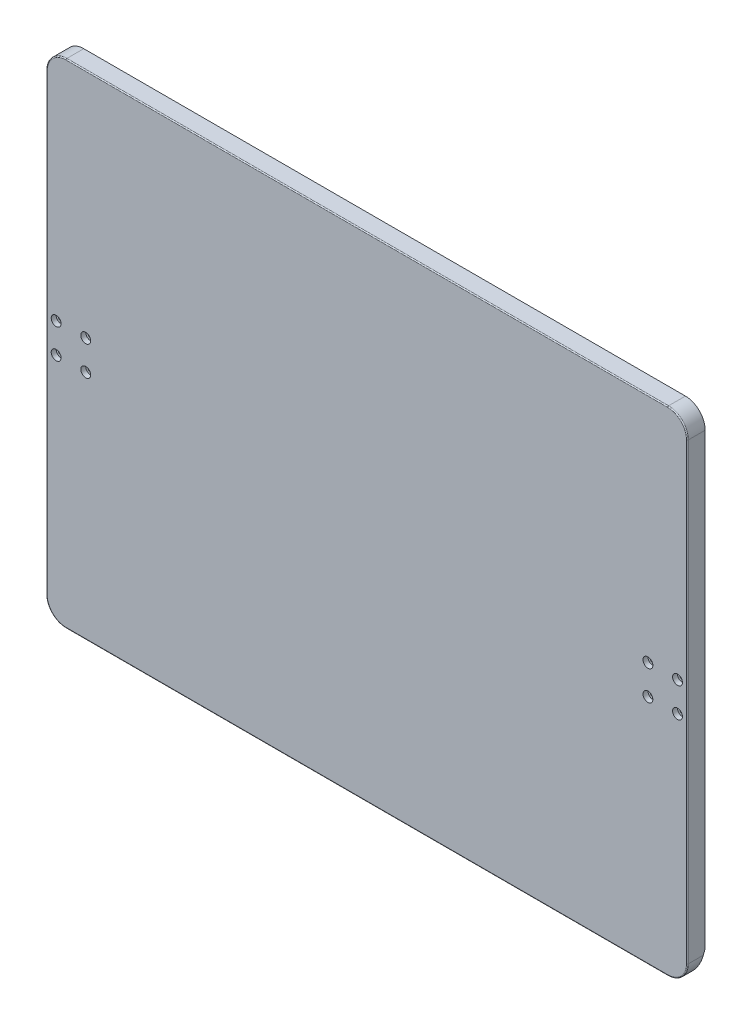
SolidWorks part; units mm, degrees
material "Beech"
ref_plane "Front Plane" through (0, 0, 0) normal (0, 0, 1) x (1, 0, 0)
ref_plane "Top Plane" through (0, 0, 0) normal (0, 1, 0) x (1, 0, 0)
ref_plane "Right Plane" through (0, 0, 0) normal (1, 0, 0) x (0, 0, -1)
sketch "Sketch1" plane through (0, 0, 0) normal (0, 0, 1) x (1, 0, 0)
  line L1 (0, 0) -> (650, 0)
  line L2 (0, 0) -> (0, 500)
  line L3 (0, 500) -> (650, 500)
  line L4 (650, 0) -> (650, 500)
  dimension "D1" = 500
  dimension "D2" = 650
extrude "base" add sketch "Sketch1" along normal blind 18
hole_wizard "counterbored M5 bolt holes" positions "Sketch2" profile "Sketch3" counterbore size "M5" standard "ANSI Metric" end condition through all
sketch "Sketch2" plane through (0, 0, 18) normal (0, 0, 1) x (1, 0, 0)
  line L1 (10, 265) -> (40, 265)
  line L2 (10, 265) -> (10, 235)
  line L3 (10, 235) -> (40, 235)
  line L4 (40, 265) -> (40, 235)
  line L5 (10, 250) -> (0, 250)
  line L6 (0, 500) -> (0, 0) construction
  point P1 (10, 265)
  point P2 (40, 235)
  point P41 (10, 235)
  point P42 (40, 265)
  dimension "D1" = 30
  dimension "D2" = 30
  dimension "D3" = 10
sketch "Sketch3" plane through (10, 265, 18) normal (1, 0, 0) x (0, -1, 0)
  line L0 (0, 0) -> (0, 18)
  line L1 (0, 18) -> (2.75, 18)
  line L3 (2.75, 18) -> (2.75, 5)
  line L4 (2.75, 5) -> (5, 5)
  line L5 (5, 5) -> (5, 0)
  line L7 (5, 0) -> (0, 0)
  line L11 (0, -6.35) -> (0, 107.95) construction
  dimension "Thru Hole Dia." = 5.5
  dimension "Thru Hole Depth" = 18
  dimension "C'Bore Dia." = 10
  dimension "C'Bore Depth" = 5
ref_plane "midplane in x" through (325, 0, 0) normal (-1, 0, 0) x (0, 0, 1)
mirror "mirror counterbored bolt holes" about plane through (325, 0, 0) normal (-1, 0, 0) of "counterbored M5 bolt holes"
fillet "round corners" radius 20 4 edges at (0, 500, 9) (650, 500, 9) (650, 0, 9) (0, 0, 9)
fillet "break top edge" radius 1 8 edges at (5.8579, 494.1421, 18) (325, 500, 18) (644.1421, 494.1421, 18) (650, 250, 18) (644.1421, 5.8579, 18) (325, 0, 18) (5.8579, 5.8579, 18) (0, 250, 18)
chamfer "front shadow chamfer" distance 25 angle 20 1 edges at (325, 0, 0) tangent propagation no first distance on face at (642.75, 265, 0)
fillet "round chamfer edges" [suppressed] radius 1
equation "\"board_thickness\" = 18mm"
equation "\"way_width\"= 75mm"
equation "\"way_thickness\"= 50mm"
equation "\"radial_clearance\"= 0.1mm"
equation "\"slider_width\"= \"way_width\"-2* \"radial_clearance\""
equation "\"slider_thickness\" = \"way_thickness\" - 2 * \"radial_clearance\""
equation "\"column_width\"= \"way_width\" + 2 * \"board_thickness\""
equation "\"boxway_slot_width\" = 50mm"
equation "\"keeper_rail_width\" = (\"column_width\" - \"boxway_slot_width\")/2"
equation "\"slider_length\" = 125mm"
equation "\"nut_diameter\"= 22mm"
equation "\"nut_length\"= 15mm"
equation "\"leadscrew_diameter\"= 10mm"
equation "\"leadscrew_radial_clearance\"= 1mm"
equation "\"bearing_bolt_pattern_width\" = 35mm"
equation "\"bearing_bolt_pattern_height\" = 60mm"
equation "\"desktop_bolt_pattern_width\" = 30mm"
equation "\"desktop_bolt_pattern_height\" = 30mm"
equation "\"bearing_bolt_nut_counterbore_diameter\" = 12mm"
equation "\"bearing_bolt_nut_counterbore_depth\"= 10mm"
equation "\"desktop_depth\"= 500mm"
equation "\"desktop_width\"= 650mm"
equation "\"D1@Sketch1\"=\"desktop_depth\""
equation "\"D2@Sketch1\"=\"desktop_width\""
equation "\"desktop_thickness\"= 18mm"
equation "\"D1@base\" = \"desktop_thickness\""
equation "\"D1@Sketch2\"=\"desktop_bolt_pattern_height\""
equation "\"D2@Sketch2\"=\"desktop_bolt_pattern_width\""
